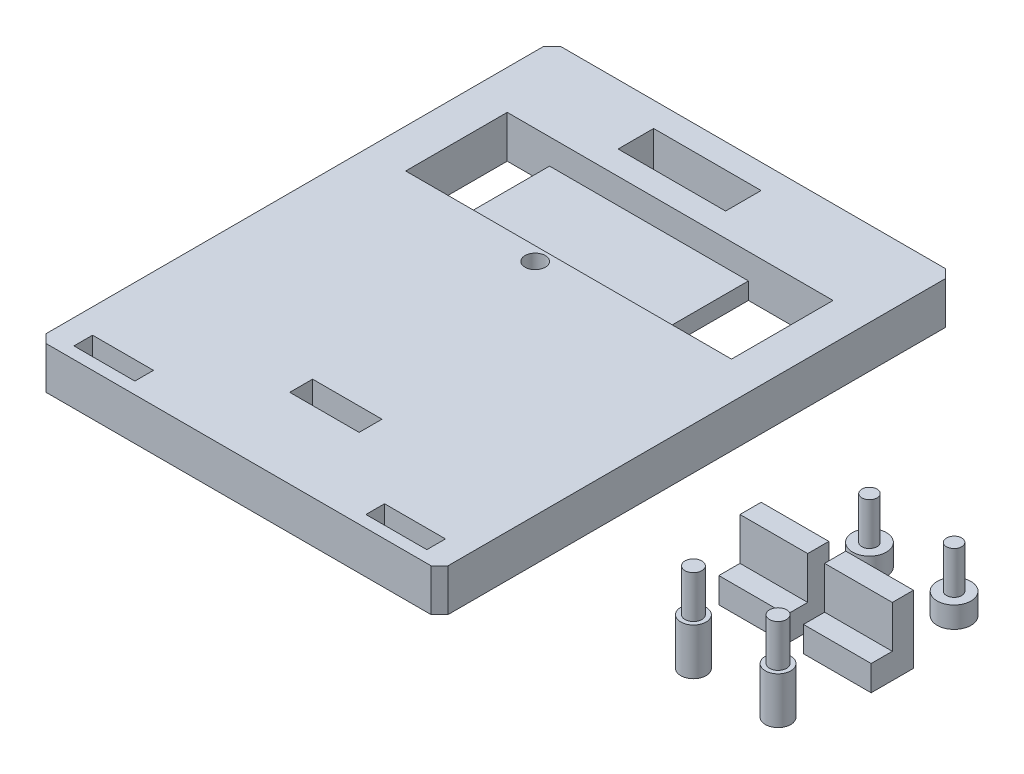
SolidWorks part; units mm, degrees
ref_plane "前视基准面" through (0, 0, 0) normal (0, 0, 1) x (1, 0, 0)
ref_plane "上视基准面" through (0, 0, 0) normal (0, 1, 0) x (1, 0, 0)
ref_plane "右视基准面" through (0, 0, 0) normal (1, 0, 0) x (0, 0, -1)
other "Configuration Table"
sketch "草图1" plane through (0, 0, 0) normal (0, 1, 0) x (1, 0, 0)
  line L1 (-54.4053, 33.3382) -> (-6.9053, 33.3382)
  line L2 (-54.4053, 33.3382) -> (-54.4053, -27.4618)
  line L3 (-54.4053, -27.4618) -> (-6.9053, -27.4618)
  line L4 (-6.9053, 33.3382) -> (-6.9053, -27.4618)
  line L5 (-54.4053, 33.3382) -> (-49.4053, 33.3382) construction
  line L6 (-54.4053, 33.3382) -> (-54.4053, 23.3382) construction
  dimension "D1" = 47.5
  dimension "D2" = 60.8
extrude "凸台-拉伸1" add sketch "草图1" against normal blind 5 contours L4 L3 L2 L1
sketch "草图2" plane through (0, 0, 0) normal (0, 1, 0) x (1, 0, 0)
  line L0 (-54.4053, 33.3382) -> (-54.4053, -27.4618) construction
  line L1 (-49.8053, 23.4382) -> (-11.3053, 23.4382)
  line L2 (-49.8053, 23.4382) -> (-49.8053, 11.4382)
  line L3 (-49.8053, 11.4382) -> (-11.3053, 11.4382)
  line L4 (-11.3053, 23.4382) -> (-11.3053, 11.4382)
  line L5 (-54.4053, 33.3382) -> (-6.9053, 33.3382) construction
  dimension "D1" = 4.6
  dimension "D2" = 9.9
  dimension "D3" = 12
  dimension "D4" = 38.5
extrude "切除-拉伸1" cut sketch "草图2" against normal blind 3 contours L2 L3 L4 L1
sketch "草图3" plane through (0, -3, 0) normal (0, 1, 0) x (1, 0, 0)
  line L0 (-49.8053, 11.4382) -> (-11.3053, 11.4382) construction
  line L3 (-49.8053, 23.4382) -> (-44.8053, 23.4382)
  line L4 (-49.8053, 23.4382) -> (-49.8053, 11.4382)
  line L5 (-49.8053, 11.4382) -> (-44.8053, 11.4382)
  line L6 (-44.8053, 23.4382) -> (-44.8053, 11.4382)
  line L7 (-49.8053, 11.4382) -> (-11.3053, 11.4382) construction
  line L8 (-11.3053, 23.4382) -> (-21.3053, 23.4382)
  line L9 (-11.3053, 23.4382) -> (-11.3053, 11.4382)
  line L10 (-11.3053, 11.4382) -> (-21.3053, 11.4382)
  line L11 (-21.3053, 23.4382) -> (-21.3053, 11.4382)
  dimension "D1" = 5
  dimension "D2" = 10
extrude "切除-拉伸2" cut sketch "草图3" against normal blind 2
sketch "草图5" plane through (0, -5, 0) normal (0, -1, 0) x (1, 0, 0)
  line L0 (-6.9053, -33.3382) -> (-6.9053, 27.4618) construction
  line L1 (-54.4053, 27.4618) -> (-6.9053, 27.4618) construction
  line L2 (-54.4053, 27.4618) -> (-6.9053, 27.4618) construction
  line L3 (-54.4053, -33.3382) -> (-6.9053, -33.3382) construction
  line L4 (8.0947, 4.4618) -> (16.0947, 4.4618)
  line L5 (8.0947, 4.4618) -> (8.0947, 9.4618)
  line L6 (8.0947, 9.4618) -> (16.0947, 9.4618)
  line L7 (16.0947, 4.4618) -> (16.0947, 9.4618)
  circle A0 centre (13.0947, -3.3382) radius 2
  circle A1 centre (13.0947, 17.4618) radius 1.5
  dimension "D1" = 20
  dimension "D2" = 20
  dimension "D3" = 10
  dimension "D4" = 30
  dimension "D5" = 5
  dimension "D6" = 8
  dimension "D7" = 15
  dimension "D8" = 18
extrude "凸台-拉伸2" add sketch "草图5" against normal blind 2.5 separate body contours A0 region at (13.0947, -5, -3.3382)
extrude "凸台-拉伸3" add sketch "草图5<3>" against normal blind 5.5 separate body contours A1 region at (13.0947, -5, 17.4618)
sketch "草图5<3>" plane through (0, -5, 0) normal (0, -1, 0) x (1, 0, 0) same geometry as "草图5"
sketch "草图6" plane through (0, 0, 0) normal (0, 1, 0) x (1, 0, 0)
  line L0 (-54.4053, 33.3382) -> (-6.9053, 33.3382) construction
  line L1 (-54.4053, 33.3382) -> (-54.4053, -27.4618) construction
  circle A0 centre (-32.9053, 9.8382) radius 1.2
  dimension "D1" = 23.5
  dimension "D2" = 21.5
extrude "切除-拉伸4" cut sketch "草图6" against normal blind 5
sketch "草图7" plane through (0, -2.5, 0) normal (0, 1, 0) x (1, 0, 0)
  circle A0 centre (13.0947, 3.3382) radius 0.9
extrude "凸台-拉伸4" add sketch "草图7" along normal blind 5
sketch "草图8" plane through (0, 0.5, 0) normal (0, 1, 0) x (1, 0, 0)
  circle A0 centre (13.0947, -17.4618) radius 1
extrude "凸台-拉伸5" add sketch "草图8" along normal blind 5
sketch "草图9" plane through (0, 0, 0) normal (0, 1, 0) x (1, 0, 0)
  line L0 (-6.9053, 33.3382) -> (-6.9053, -27.4618) construction
  line L1 (-54.4053, -27.4618) -> (-6.9053, -27.4618) construction
  line L3 (-34.0053, -15.3618) -> (-25.8053, -15.3618)
  line L4 (-34.0053, -15.3618) -> (-34.0053, -18.0618)
  line L5 (-34.0053, -18.0618) -> (-25.8053, -18.0618)
  line L6 (-25.8053, -15.3618) -> (-25.8053, -18.0618)
  dimension "D3" = 8.2
  dimension "D4" = 2.7
  dimension "D5" = 9.4
  dimension "D6" = 18.9
extrude "切除-拉伸5" cut sketch "草图9" against normal blind 5
chamfer "倒角1" distance 1 angle 45 4 edges at (-54.4053, -2.5, 27.4618) (-54.4053, -2.5, -33.3382) (-6.9053, -2.5, -33.3382) (-6.9053, -2.5, 27.4618)
sketch "草图10" plane through (0, 0, 0) normal (0, 1, 0) x (1, 0, 0)
  line L0 (-53.4053, 33.3382) -> (-7.9053, 33.3382) construction
  line L1 (-39.5053, 30.4382) -> (-26.8053, 30.4382)
  line L2 (-39.5053, 30.4382) -> (-39.5053, 26.2382)
  line L3 (-39.5053, 26.2382) -> (-26.8053, 26.2382)
  line L4 (-26.8053, 30.4382) -> (-26.8053, 26.2382)
  line L5 (-54.4053, 32.3382) -> (-54.4053, -26.4618) construction
  line L6 (-6.9053, 32.3382) -> (-6.9053, -26.4618) construction
  line L7 (-53.4053, -27.4618) -> (-7.9053, -27.4618) construction
  line L8 (-51.5053, -23.8618) -> (-44.3053, -23.8618)
  line L9 (-51.5053, -23.8618) -> (-51.5053, -26.0618)
  line L10 (-51.5053, -26.0618) -> (-44.3053, -26.0618)
  line L11 (-44.3053, -23.8618) -> (-44.3053, -26.0618)
  line L12 (-17.0053, -23.8618) -> (-9.8053, -23.8618)
  line L13 (-17.0053, -23.8618) -> (-17.0053, -26.0618)
  line L14 (-17.0053, -26.0618) -> (-9.8053, -26.0618)
  line L15 (-9.8053, -23.8618) -> (-9.8053, -26.0618)
  dimension "D3" = 14.9
  dimension "D1" = 2.9
  dimension "D2" = 4.2
  dimension "D4" = 19.9
  dimension "D5" = 7.2
  dimension "D6" = 2.2
  dimension "D7" = 1.4
  dimension "D8" = 2.9
  dimension "D9" = 2.9
  dimension "D10" = 1.4
  dimension "D11" = 7.2
  dimension "D12" = 2.2
extrude "切除-拉伸6" cut sketch "草图10" against normal blind 5
extrude "凸台-拉伸6" add sketch "草图5<4>" against normal blind 3 separate body contours L4 L7 L6 L5 region at (12.0947, -5, 6.9618)
sketch "草图5<4>" plane through (0, -5, 0) normal (0, -1, 0) x (1, 0, 0) same geometry as "草图5"
sketch "草图11" plane through (0, -2, 0) normal (0, 1, 0) x (1, 0, 0)
  line L0 (16.0947, -4.4618) -> (16.0947, -9.4618) construction
  line L1 (8.0947, -4.4618) -> (16.0947, -4.4618)
  line L2 (8.0947, -4.4618) -> (8.0947, -6.9618)
  line L3 (8.0947, -6.9618) -> (16.0947, -6.9618)
  line L4 (16.0947, -4.4618) -> (16.0947, -6.9618)
  line L5 (8.0947, -4.4618) -> (16.0947, -4.4618) construction
  dimension "D1" = 2.5
  dimension "D2" = 8
  dimension "D3" = 0
  dimension "D4" = 0
extrude "凸台-拉伸7" add sketch "草图11" along normal blind 5
pattern_linear "阵列(线性)1" count 2 spacing 10 along (1, 0, 0) of bodies 118 113 114
